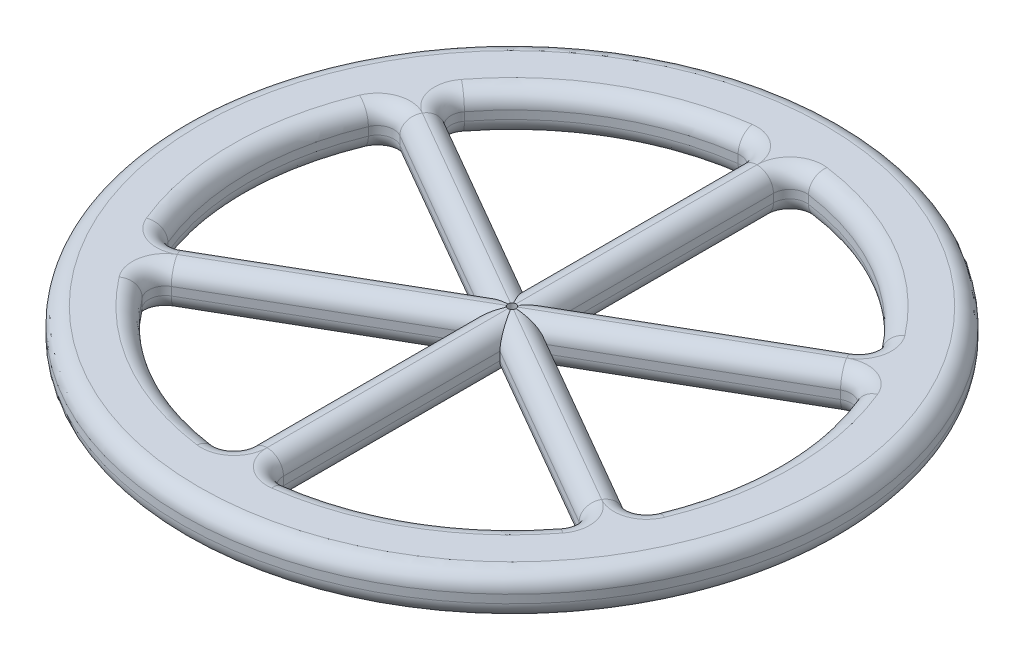
SolidWorks part; units mm, degrees
ref_plane "Front Plane" through (0, 0, 0) normal (0, 0, 1) x (1, 0, 0)
ref_plane "Top Plane" through (0, 0, 0) normal (0, 1, 0) x (1, 0, 0)
ref_plane "Right Plane" through (0, 0, 0) normal (1, 0, 0) x (0, 0, -1)
sketch "Sketch1" plane through (0, 0, 0) normal (0, 1, 0) x (1, 0, 0)
  line L0 (0, 0) -> (0, 320) construction
  line L1 (-20, 34.641) -> (-20, 319.3744)
  line L2 (20, 34.641) -> (20, 319.3744)
  line L3 (20, 34.641) -> (266.5863, 177.0077)
  line L4 (40, 0) -> (286.5863, 142.3667)
  line L5 (0, 0) -> (277.1281, 160) construction
  line L6 (40, 0) -> (286.5863, -142.3667)
  line L7 (20, -34.641) -> (266.5863, -177.0077)
  line L8 (0, 0) -> (277.1281, -160) construction
  line L9 (20, -34.641) -> (20, -319.3744)
  line L10 (-20, -34.641) -> (-20, -319.3744)
  line L11 (0, 0) -> (0, -320) construction
  line L12 (-20, -34.641) -> (-266.5863, -177.0077)
  line L13 (-40, 0) -> (-286.5863, -142.3667)
  line L14 (0, 0) -> (-277.1281, -160) construction
  line L15 (-40, 0) -> (-286.5863, 142.3667)
  line L16 (-20, 34.641) -> (-266.5863, 177.0077)
  line L17 (0, 0) -> (-277.1281, 160) construction
  circle A0 centre (0, 0) radius 400
  circle A1 centre (0, 0) radius 320
  circle A2 centre (0, 0) radius 40
  circle A3 centre (0, 0) radius 320
  circle A4 centre (0, 0) radius 320
  circle A5 centre (0, 0) radius 320
  circle A6 centre (0, 0) radius 320
  circle A7 centre (0, 0) radius 320
  point P43 (0, 0)
  dimension "D1" = 800
  dimension "D2" = 80
  dimension "D3" = 80
  dimension "D4" = 40
  dimension "D5" = 6
extrude "Boss-Extrude1" add sketch "Sketch1" along normal blind 50 contours A0 A1 | A2 L2 A1 L1 | A2 L16 A1 L15 | A2 L13 A1 L12 | A2 L10 A1 L9 | A2 L7 A1 L6 | A2 L4 A1 L3 | A2 region at (-155.039, 0, -89.5118) region at (0, 0, -179.0236) region at (0, 0, 0) region at (155.039, 0, -89.5118) region at (-155.039, 0, 89.5118) region at (155.039, 0, 89.5118) region at (0, 0, 179.0236) region at (-388.6863, 0, 0)
fillet "Fillet2" radius 20 48 edges at (163.2932, 50, -71.1833) (163.2932, 0, -71.1833) (163.2932, 50, 71.1833) (163.2932, 0, 71.1833) (143.2932, 50, 105.8244) (143.2932, 0, 105.8244) (20, 50, 177.0077) (20, 0, 177.0077) (-20, 50, 177.0077) (-20, 0, 177.0077) (-143.2932, 50, 105.8244) (-143.2932, 0, 105.8244) (-163.2932, 50, 71.1833) (-163.2932, 0, 71.1833) (-163.2932, 50, -71.1833) (-163.2932, 0, -71.1833) (-143.2932, 50, -105.8244) (-143.2932, 0, -105.8244) (-20, 50, -177.0077) (-20, 0, -177.0077) (20, 50, -177.0077) (20, 0, -177.0077) (143.2932, 50, -105.8244) (143.2932, 0, -105.8244) (286.5863, 25, -142.3667) (320, 50, 0) (286.5863, 25, 142.3667) (320, 0, 0) (266.5863, 25, 177.0077) (160, 50, 277.1281) (20, 25, 319.3744) (160, 0, 277.1281) (-20, 25, 319.3744) (-160, 50, 277.1281) (-266.5863, 25, 177.0077) (-160, 0, 277.1281) (-286.5863, 25, 142.3667) (-320, 50, 0) (-286.5863, 25, -142.3667) (-320, 0, 0) (-266.5863, 25, -177.0077) (-160, 50, -277.1281) (-20, 25, -319.3744) (-160, 0, -277.1281) (20, 25, -319.3744) (160, 50, -277.1281) (266.5863, 25, -177.0077) (160, 0, -277.1281)
fillet "Fillet3" radius 20 2 edges at (0, 50, 400) (0, 0, 400)
sketch "Sketch2" plane through (0, 0, 0) normal (0, -1, 0) x (1, 0, 0)
  circle A0 centre (0, 0) radius 5
  dimension "D1" = 10
extrude "Cut-Extrude1" cut sketch "Sketch2" against normal through all
